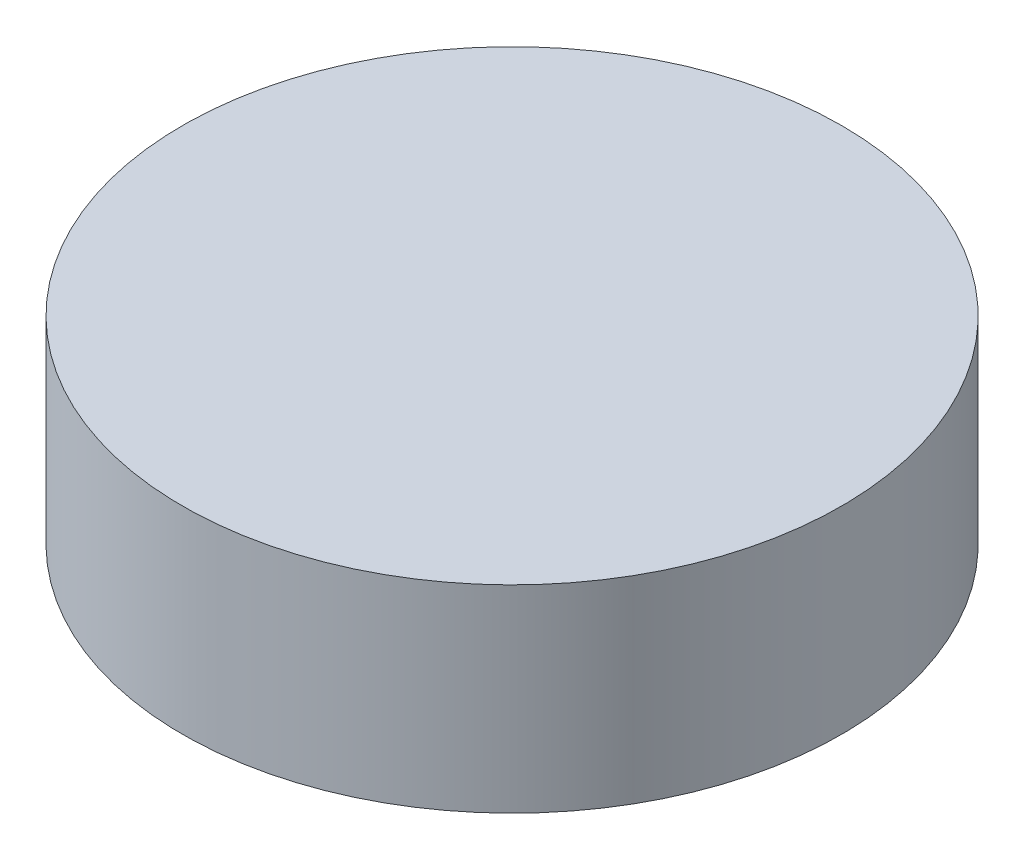
SolidWorks part; units mm, degrees
material "ALUMINUM 6061-T6"
ref_plane "Front Plane" through (0, 0, 0) normal (0, 0, 1) x (1, 0, 0)
ref_plane "Top Plane" through (0, 0, 0) normal (0, 1, 0) x (1, 0, 0)
ref_plane "Right Plane" through (0, 0, 0) normal (1, 0, 0) x (0, 0, -1)
sketch "Sketch1" plane through (0, 0, 0) normal (0, 1, 0) x (1, 0, 0)
  circle A0 centre (0, 0) radius 63.5
  dimension "D1" = 127
extrude "Boss-Extrude1" add sketch "Sketch1" along normal mid plane 38.1
